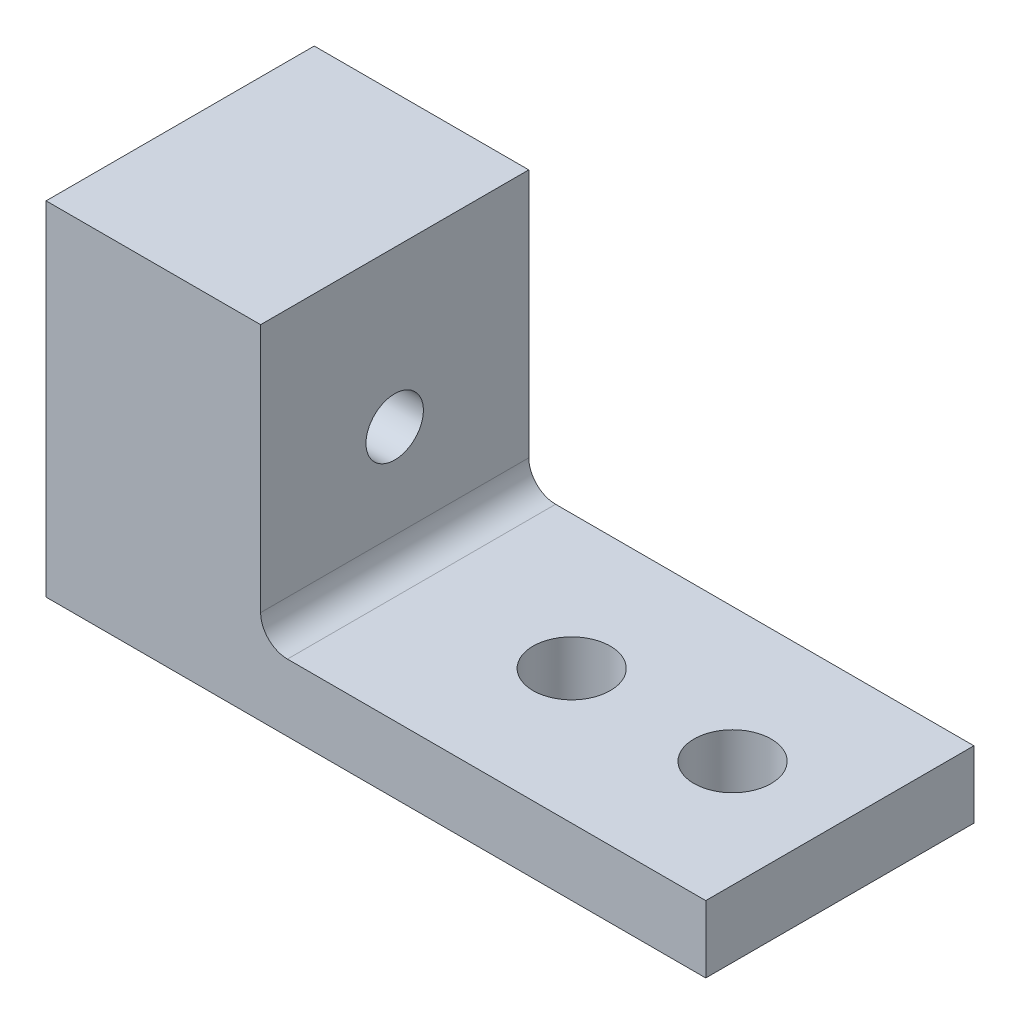
SolidWorks part; units mm, degrees
material "Plain Carbon Steel"
ref_plane "Front Plane" through (0, 0, 0) normal (0, 0, 1) x (1, 0, 0)
ref_plane "Top Plane" through (0, 0, 0) normal (0, 1, 0) x (1, 0, 0)
ref_plane "Right Plane" through (0, 0, 0) normal (1, 0, 0) x (0, 0, -1)
sketch "Sketch1" plane through (0, 0, 0) normal (0, 0, 1) x (1, 0, 0)
  line L0 (0, 0) -> (0, 16.256)
  line L1 (0, 16.256) -> (10.16, 16.256)
  line L2 (10.16, 16.256) -> (10.16, 3.175)
  line L3 (10.16, 3.175) -> (31.242, 3.175)
  line L4 (31.242, 3.175) -> (31.242, 0)
  line L5 (31.242, 0) -> (0, 0)
  dimension "D1" = 10.16
  dimension "D2" = 3.175
  dimension "D4" = 16.256
  dimension "D3" = 21.082
extrude "Boss-Extrude1" add sketch "Sketch1" against normal mid plane 12.7
sketch "Sketch2" plane through (0, 0, 0) normal (-1, 0, 0) x (0, 0, 1)
  circle A0 centre (0, 8.89) radius 1.3589
  dimension "D1" = 2.7178
  dimension "D2" = 8.89
extrude "Cut-Extrude1" cut sketch "Sketch2" against normal up to next
sketch "Sketch3" plane through (0, 0, 0) normal (0, -1, 0) x (1, 0, 0)
  circle A0 centre (18.542, 0) radius 1.8288
  dimension "D1" = 3.6576
  dimension "D2" = 8.382
extrude "Cut-Extrude2" cut sketch "Sketch3" against normal up to next
fillet "Fillet2" radius 1.27 1 edges at (10.16, 3.175, 0)
pattern_linear "LPattern1" count 2 spacing 7.62 along (1, 0, 0) of "Cut-Extrude2"
equation "\"D2@Sketch1\"=1/8"
equation "\"Middle Coupler Inner Daimeter\"= 3.875in"
equation "\"Middle Coupler  Wall Thickness\"= 0.25in"
equation "\"Middle Coupler Bottom Thickness\"= 0.2in"
equation "\"Bearing Rail Offset\"= 0.45in"
equation "\"3-56 UNF Tap\"= 0.089in"
equation "\"3-48 Tap\"= 0.079in"
equation "\"3-56 UNF Clearance\"= 0.104in"
equation "\"3-48 Clearance\"= 0.104in"
equation "\"Ball Bearing Distance\"= 0.03in"
equation "\"TCA Outer Diameter\"= 6in"
equation "\"Interstage Aeroframe Wall Thickness\"= 0.072in"
equation "\"Compression Spring OD\"= 0.42in"
equation "\"10-24 Tap\"= 0.157in"
equation "\"10-24 Clearance\"= 0.196in"
equation "\"Lower Stage Fuselage Wall Thickness\"= 0.25in"
equation "\"6-32 Tap\"= 0.107in"
equation "\"6-32 Clearance\"= 0.144"
equation "\"1/4-20 Tap\"= 0.201in"
equation "\"12-24 Tap\"= 0.177in"
equation "\"12-24 Major Diameter\"= 0.216in"
equation "\"D1@Sketch2\"=\"6-32 Tap\""
equation "\"D1@Sketch3\"=\"6-32 Clearance\""
